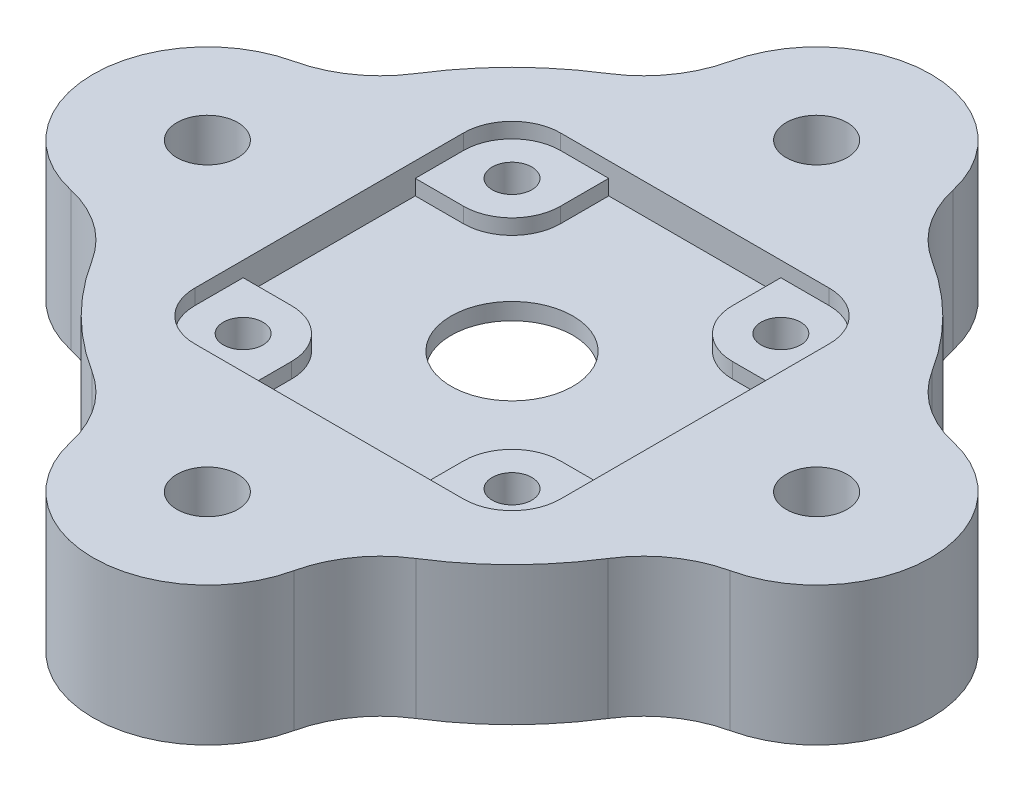
SolidWorks part; units mm, degrees
ref_plane "Front Plane" through (0, 0, 0) normal (0, 0, 1) x (1, 0, 0)
ref_plane "Top Plane" through (0, 0, 0) normal (0, 1, 0) x (1, 0, 0)
ref_plane "Right Plane" through (0, 0, 0) normal (1, 0, 0) x (0, 0, -1)
sketch "Sketch1" plane through (0, 0, 0) normal (0, 1, 0) x (1, 0, 0)
  circle A0 centre (0, 0) radius 20
  circle A1 centre (0, 0) radius 27.5
  circle A2 centre (0, 20) radius 2
  circle A3 centre (20, 0) radius 2
  circle A4 centre (0, -20) radius 2
  circle A5 centre (-20, 0) radius 2
  circle A6 centre (0, 0) radius 13.5
  dimension "D1" = 55
  dimension "D2" = 40
  dimension "D3" = 27
  dimension "D4" = 4
extrude "Boss-Extrude1" add sketch "Sketch1" along normal blind 6 contours A1 A5 A0 A2 A3 A4 | A5 A0 A4 A3 A2 A6 region at (17.4371, 0, 0) region at (-26.7222, 0, 0)
sketch "Sketch2" plane through (0, 6, 0) normal (0, 1, 0) x (1, 0, 0)
  line L1 (8.825, 8.825) -> (-8.825, 8.825)
  line L2 (8.825, 8.825) -> (8.825, -8.825)
  line L3 (8.825, -8.825) -> (-8.825, -8.825)
  line L4 (-8.825, 8.825) -> (-8.825, -8.825)
  line L5 (8.825, 8.825) -> (-8.825, -8.825) construction
  line L6 (8.825, -8.825) -> (-8.825, 8.825) construction
  circle A0 centre (0, -20) radius 2 construction
  circle A1 centre (0, 0) radius 27.5
  circle A2 centre (0, 0) radius 27.5
  circle A3 centre (20, 0) radius 2 construction
  circle A4 centre (0, 20) radius 2 construction
  circle A5 centre (-20, 0) radius 2 construction
  circle A6 centre (0, -20) radius 2
  circle A7 centre (20, 0) radius 2
  circle A8 centre (0, 20) radius 2
  circle A9 centre (-20, 0) radius 2
  circle A10 centre (0, 0) radius 4
  circle A11 centre (-8.825, 8.825) radius 1.3
  circle A12 centre (8.825, 8.825) radius 1.3
  circle A13 centre (8.825, -8.825) radius 1.3
  circle A14 centre (-8.825, -8.825) radius 1.3
  circle M2 centre (-20, 0) radius 2
  circle M3 centre (0, 20) radius 2
  circle M4 centre (20, 0) radius 2
  circle M5 centre (0, -20) radius 2
  circle M6 centre (0, 0) radius 27.5
  circle M7 centre (0, 0) radius 13.5
  dimension "D2" = 8
  dimension "D4" = 2.6
  dimension "D3" = 17.65
  dimension "D1" = 0
extrude "Boss-Extrude2" add sketch "Sketch2" along normal blind 3.1 contours A14 A11 A12 A13 M6 M7 M3 M5 M4 M2 | A14 L4 A11 M7 | A12 A11 L1 M7 | A13 A12 L2 M7 | A14 A13 L3 M7 | A14 L3 A13 L2 A12 L1 A11 L4 A10 region at (0, 6, -10.8309) region at (0, 6, -8.5754) region at (-10.8309, 6, 0) region at (10.8309, 6, 0) region at (0, 6, 10.8309) region at (-26.7222, 6, 0)
sketch "Sketch3" plane through (0, 9.1, 0) normal (0, 1, 0) x (1, 0, 0)
  line L0 (0, 12) -> (0, -12) construction
  line L1 (12, 12) -> (-12, 12)
  line L2 (12, 12) -> (12, -12)
  line L3 (12, -12) -> (-12, -12)
  line L4 (-12, 12) -> (-12, -12)
  line L5 (12, 12) -> (-12, -12) construction
  line L6 (12, -12) -> (-12, 12) construction
  line L7 (-12, 0) -> (12, 0) construction
  circle A0 centre (-8.825, 8.825) radius 1.5
  circle A2 centre (-8.825, 8.825) radius 3.175
  circle A3 centre (8.825, 8.825) radius 1.5
  circle A4 centre (8.825, 8.825) radius 3.175
  circle A5 centre (8.825, -8.825) radius 1.5
  circle A6 centre (8.825, -8.825) radius 3.175
  circle A7 centre (-8.825, -8.825) radius 3.175
  circle A8 centre (-8.825, -8.825) radius 1.5
  point P0 (0, 0)
  circle M8 centre (-8.825, -8.825) radius 1.3
  circle M9 centre (-8.825, 8.825) radius 1.3
  circle M10 centre (8.825, -8.825) radius 1.3
  circle M11 centre (8.825, 8.825) radius 1.3
  circle M17 centre (0, 0) radius 4
  dimension "D2" = 3
  dimension "D1" = 24
  dimension "D3" = 17.65
extrude "Cut-Extrude1" cut sketch "Sketch3" against normal offset from surface (1 mm away) 2.1 contours A2 M9 | L4 A7 L3 A6 L2 A4 L1 A2 M17 | A4 M11 | A6 M10 | A7 M8 | A0 M9 | A3 M11 | A5 M10 | A8 M8 region at (6.3399, 9.1, -6.3399) region at (11.0066, 9.1, -11.0066) region at (-6.6434, 9.1, -11.0066) region at (11.0066, 9.1, 11.0066) region at (-8.825, 9.1, 5.7398) region at (-10.2826, 9.1, -8.825) region at (7.3674, 9.1, -8.825) region at (7.3674, 9.1, 8.825) region at (-10.2826, 9.1, 8.825) up to face at (0, 6, 0)
sketch "Sketch4" plane through (0, 8.1, 0) normal (0, 1, 0) x (1, 0, 0)
  line L0 (-8.825, 5.65) -> (-12, 5.65)
  line L1 (-5.65, 8.825) -> (-5.65, 12)
  line L2 (5.65, 8.825) -> (5.65, 12)
  line L3 (8.825, 5.65) -> (12, 5.65)
  line L4 (-12, 8.825) -> (-12, -8.825)
  line L5 (-8.825, -12) -> (8.825, -12)
  line L6 (12, -8.825) -> (12, 8.825)
  line L7 (8.825, 12) -> (-8.825, 12)
  line L8 (-12, 8.825) -> (-12, -8.825)
  line L9 (-8.825, -12) -> (8.825, -12)
  line L10 (12, -8.825) -> (12, 8.825)
  line L11 (8.825, 12) -> (-8.825, 12)
  line L12 (8.825, -5.65) -> (12, -5.65)
  line L13 (5.65, -8.825) -> (5.65, -12)
  line L14 (-5.65, -8.825) -> (-5.65, -12)
  line L15 (-8.825, -5.65) -> (-12, -5.65)
  circle A0 centre (-8.825, 8.825) radius 3.175
  arc A1 (-8.825, 12) -> (-12, 8.825) centre (-8.825, 8.825) ccw construction
  circle A2 centre (8.825, 8.825) radius 3.175
  circle A3 centre (8.825, -8.825) radius 3.175
  circle A4 centre (-8.825, -8.825) radius 3.175
  arc A5 (-12, -8.825) -> (-8.825, -12) centre (-8.825, -8.825) ccw construction
  arc A6 (8.825, -12) -> (12, -8.825) centre (8.825, -8.825) ccw construction
  arc A7 (12, 8.825) -> (8.825, 12) centre (8.825, 8.825) ccw construction
  arc A12 (-8.825, 12) -> (-12, 8.825) centre (-8.825, 8.825) ccw
  arc A13 (-12, -8.825) -> (-8.825, -12) centre (-8.825, -8.825) ccw
  arc A14 (8.825, -12) -> (12, -8.825) centre (8.825, -8.825) ccw
  arc A15 (12, 8.825) -> (8.825, 12) centre (8.825, 8.825) ccw
  arc A16 (-8.825, 12) -> (-12, 8.825) centre (-8.825, 8.825) ccw
  arc A17 (-12, -8.825) -> (-8.825, -12) centre (-8.825, -8.825) ccw
  arc A18 (8.825, -12) -> (12, -8.825) centre (8.825, -8.825) ccw
  arc A19 (12, 8.825) -> (8.825, 12) centre (8.825, 8.825) ccw
  circle M16 centre (0, 0) radius 4
  line M18 (-12, 8.825) -> (-12, -8.825)
  line M20 (-8.825, -12) -> (8.825, -12)
  line M22 (12, -8.825) -> (12, 8.825)
  line M24 (8.825, 12) -> (-8.825, 12)
  dimension "D1" = 0
extrude "Cut-Extrude2" cut sketch "Sketch4" against normal blind 1 contours A4 A3 A2 A0 M20 M22 M24 M18 M16 region at (-6.3399, 8.1, -6.3399)
sketch "Sketch5" plane through (0, 8.1, 0) normal (0, 1, 0) x (1, 0, 0)
  circle A0 centre (8.825, -8.825) radius 1.3 construction
  circle A1 centre (-8.825, -8.825) radius 1.3 construction
  circle A2 centre (-8.825, 8.825) radius 1.3 construction
  circle A3 centre (8.825, 8.825) radius 1.3 construction
  circle A4 centre (8.825, -8.825) radius 1.3
  circle A5 centre (-8.825, -8.825) radius 1.3
  circle A6 centre (-8.825, 8.825) radius 1.3
  circle A7 centre (8.825, 8.825) radius 1.3
extrude "Cut-Extrude3" cut sketch "Sketch5" against normal up to next
sketch "Sketch6" plane through (0, 9.1, 0) normal (0, 1, 0) x (1, 0, 0)
  circle A0 centre (0, 20) radius 7.5
  circle A1 centre (0, 0) radius 27.5 construction
  circle A2 centre (0, -20) radius 7.5
  circle A3 centre (-20, 0) radius 7.5
  circle A4 centre (20, 0) radius 7.5
  circle A5 centre (0, 0) radius 20
  circle A7 centre (0, 0) radius 27.5
  circle A8 centre (0, 0) radius 27.5
  circle M13 centre (0, 0) radius 27.5
  dimension "D1" = 0
extrude "Cut-Extrude4" cut sketch "Sketch6" against normal up to next contours A5 A0 A3 M13 | A5 A4 A0 M13 | A5 A2 A4 M13 | A5 A3 A2 M13 region at (16.3352, 9.1, -16.3352) region at (-16.3352, 9.1, -16.3352) region at (16.3352, 9.1, 16.3352) region at (-16.3352, 9.1, 16.3352)
fillet "Fillet1" radius 7.5 8 edges at (-18.5938, 4.55, -7.367) (-7.367, 4.55, -18.5938) (7.367, 4.55, -18.5938) (18.5938, 4.55, -7.367) (18.5938, 4.55, 7.367) (7.367, 4.55, 18.5938) (-7.367, 4.55, 18.5938) (-18.5938, 4.55, 7.367)
sketch "Sketch7" [suppressed] plane through (0, 0, 0) normal (0, -1, 0) x (1, 0, 0)
  arc A16 (16.9318, 10.6449) -> (10.6449, 16.9318) centre (0, 0) ccw
  arc A17 (7.3184, 21.6406) -> (10.6449, 16.9318) centre (14.6367, 23.2812) ccw
  arc A18 (7.3184, 21.6406) -> (-7.3184, 21.6406) centre (0, 20) ccw
  arc A19 (-10.6449, 16.9318) -> (-7.3184, 21.6406) centre (-14.6367, 23.2812) ccw
  arc A20 (-10.6449, 16.9318) -> (-16.9318, 10.6449) centre (0, 0) ccw
  arc A21 (-21.6406, 7.3184) -> (-16.9318, 10.6449) centre (-23.2812, 14.6367) ccw
  arc A22 (-21.6406, 7.3184) -> (-21.6406, -7.3184) centre (-20, 0) ccw
  arc A23 (-16.9318, -10.6449) -> (-21.6406, -7.3184) centre (-23.2812, -14.6367) ccw
  arc A24 (-16.9318, -10.6449) -> (-10.6449, -16.9318) centre (0, 0) ccw
  arc A25 (-7.3184, -21.6406) -> (-10.6449, -16.9318) centre (-14.6367, -23.2812) ccw
  arc A26 (-7.3184, -21.6406) -> (7.3184, -21.6406) centre (0, -20) ccw
  arc A27 (10.6449, -16.9318) -> (7.3184, -21.6406) centre (14.6367, -23.2812) ccw
  arc A28 (10.6449, -16.9318) -> (16.9318, -10.6449) centre (0, 0) ccw
  arc A29 (21.6406, -7.3184) -> (16.9318, -10.6449) centre (23.2812, -14.6367) ccw
  arc A30 (21.6406, -7.3184) -> (21.6406, 7.3184) centre (20, 0) ccw
  arc A31 (16.9318, 10.6449) -> (21.6406, 7.3184) centre (23.2812, 14.6367) ccw
  arc A32 (16.9318, 10.6449) -> (10.6449, 16.9318) centre (0, 0) ccw
  arc A33 (7.3184, 21.6406) -> (10.6449, 16.9318) centre (14.6367, 23.2812) ccw
  arc A34 (7.3184, 21.6406) -> (-7.3184, 21.6406) centre (0, 20) ccw
  arc A35 (-10.6449, 16.9318) -> (-7.3184, 21.6406) centre (-14.6367, 23.2812) ccw
  arc A36 (-10.6449, 16.9318) -> (-16.9318, 10.6449) centre (0, 0) ccw
  arc A37 (-21.6406, 7.3184) -> (-16.9318, 10.6449) centre (-23.2812, 14.6367) ccw
  arc A38 (-21.6406, 7.3184) -> (-21.6406, -7.3184) centre (-20, 0) ccw
  arc A39 (-16.9318, -10.6449) -> (-21.6406, -7.3184) centre (-23.2812, -14.6367) ccw
  arc A40 (-16.9318, -10.6449) -> (-10.6449, -16.9318) centre (0, 0) ccw
  arc A41 (-7.3184, -21.6406) -> (-10.6449, -16.9318) centre (-14.6367, -23.2812) ccw
  arc A42 (-7.3184, -21.6406) -> (7.3184, -21.6406) centre (0, -20) ccw
  arc A43 (10.6449, -16.9318) -> (7.3184, -21.6406) centre (14.6367, -23.2812) ccw
  arc A44 (10.6449, -16.9318) -> (16.9318, -10.6449) centre (0, 0) ccw
  arc A45 (21.6406, -7.3184) -> (16.9318, -10.6449) centre (23.2812, -14.6367) ccw
  arc A46 (21.6406, -7.3184) -> (21.6406, 7.3184) centre (20, 0) ccw
  arc A47 (16.9318, 10.6449) -> (21.6406, 7.3184) centre (23.2812, 14.6367) ccw
  dimension "D1" = 0
extrude "Cut-Extrude5" [suppressed] cut sketch "Sketch7" against normal up to surface (6 mm away) up to face at (0, 6, 0)
sketch "Sketch8" [suppressed] plane through (0, 9.1, 0) normal (0, 1, 0) x (1, 0, 0)
  arc A16 (-21.6406, 7.3184) -> (-21.6406, -7.3184) centre (-20, 0) ccw
  arc A17 (-16.9318, -10.6449) -> (-21.6406, -7.3184) centre (-23.2812, -14.6367) ccw
  arc A18 (-16.9318, -10.6449) -> (-10.6449, -16.9318) centre (0, 0) ccw
  arc A19 (-7.3184, -21.6406) -> (-10.6449, -16.9318) centre (-14.6367, -23.2812) ccw
  arc A20 (-7.3184, -21.6406) -> (7.3184, -21.6406) centre (0, -20) ccw
  arc A21 (10.6449, -16.9318) -> (7.3184, -21.6406) centre (14.6367, -23.2812) ccw
  arc A22 (10.6449, -16.9318) -> (16.9318, -10.6449) centre (0, 0) ccw
  arc A23 (21.6406, -7.3184) -> (16.9318, -10.6449) centre (23.2812, -14.6367) ccw
  arc A24 (21.6406, -7.3184) -> (21.6406, 7.3184) centre (20, 0) ccw
  arc A25 (16.9318, 10.6449) -> (21.6406, 7.3184) centre (23.2812, 14.6367) ccw
  arc A26 (16.9318, 10.6449) -> (10.6449, 16.9318) centre (0, 0) ccw
  arc A27 (7.3184, 21.6406) -> (10.6449, 16.9318) centre (14.6367, 23.2812) ccw
  arc A28 (7.3184, 21.6406) -> (-7.3184, 21.6406) centre (0, 20) ccw
  arc A29 (-10.6449, 16.9318) -> (-7.3184, 21.6406) centre (-14.6367, 23.2812) ccw
  arc A30 (-10.6449, 16.9318) -> (-16.9318, 10.6449) centre (0, 0) ccw
  arc A31 (-21.6406, 7.3184) -> (-16.9318, 10.6449) centre (-23.2812, 14.6367) ccw
  arc A32 (-21.6406, 7.3184) -> (-21.6406, -7.3184) centre (-20, 0) ccw
  arc A33 (-16.9318, -10.6449) -> (-21.6406, -7.3184) centre (-23.2812, -14.6367) ccw
  arc A34 (-16.9318, -10.6449) -> (-10.6449, -16.9318) centre (0, 0) ccw
  arc A35 (-7.3184, -21.6406) -> (-10.6449, -16.9318) centre (-14.6367, -23.2812) ccw
  arc A36 (-7.3184, -21.6406) -> (7.3184, -21.6406) centre (0, -20) ccw
  arc A37 (10.6449, -16.9318) -> (7.3184, -21.6406) centre (14.6367, -23.2812) ccw
  arc A38 (10.6449, -16.9318) -> (16.9318, -10.6449) centre (0, 0) ccw
  arc A39 (21.6406, -7.3184) -> (16.9318, -10.6449) centre (23.2812, -14.6367) ccw
  arc A40 (21.6406, -7.3184) -> (21.6406, 7.3184) centre (20, 0) ccw
  arc A41 (16.9318, 10.6449) -> (21.6406, 7.3184) centre (23.2812, 14.6367) ccw
  arc A42 (16.9318, 10.6449) -> (10.6449, 16.9318) centre (0, 0) ccw
  arc A43 (7.3184, 21.6406) -> (10.6449, 16.9318) centre (14.6367, 23.2812) ccw
  arc A44 (7.3184, 21.6406) -> (-7.3184, 21.6406) centre (0, 20) ccw
  arc A45 (-10.6449, 16.9318) -> (-7.3184, 21.6406) centre (-14.6367, 23.2812) ccw
  arc A46 (-10.6449, 16.9318) -> (-16.9318, 10.6449) centre (0, 0) ccw
  arc A47 (-21.6406, 7.3184) -> (-16.9318, 10.6449) centre (-23.2812, 14.6367) ccw
  dimension "D1" = 0
extrude "Cut-Extrude6" [suppressed] cut sketch "Sketch8" against normal up to surface (3.1 mm away) up to face at (0, 6, 0)
